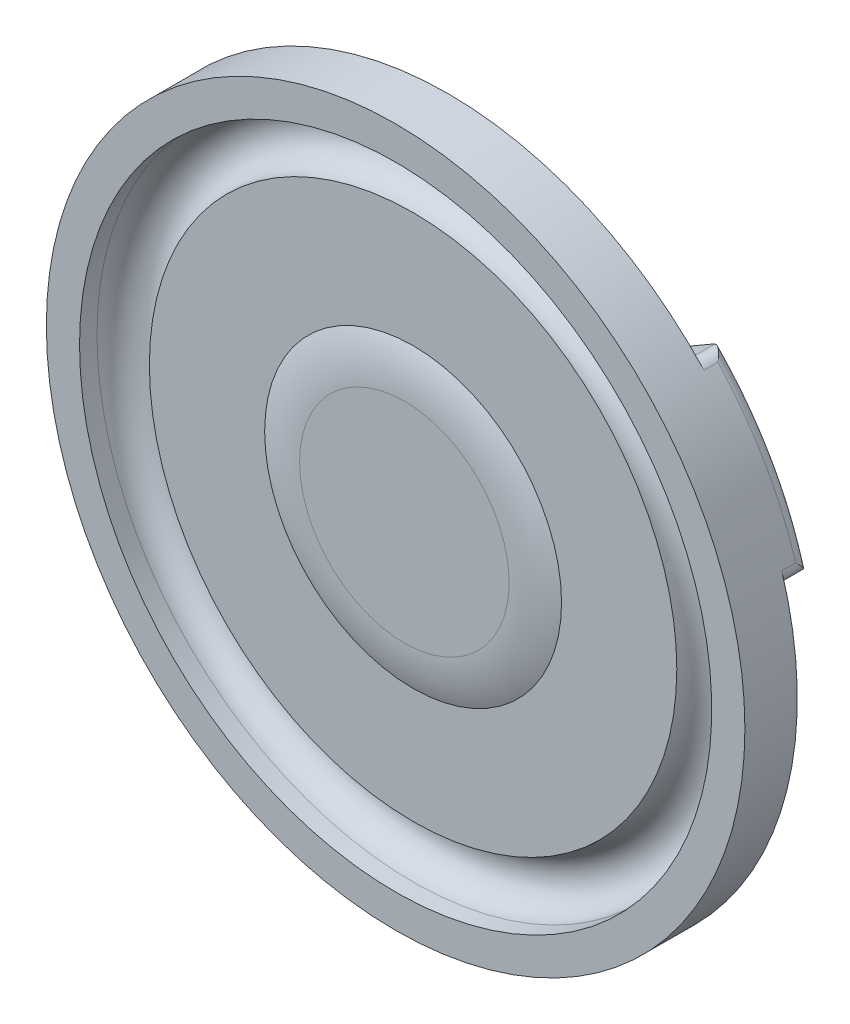
SolidWorks part; units mm, degrees
material "ABS"
ref_plane "Спереди" through (0, 0, 0) normal (0, 0, 1) x (1, 0, 0)
ref_plane "Сверху" through (0, 0, 0) normal (0, 1, 0) x (1, 0, 0)
ref_plane "Справа" through (0, 0, 0) normal (1, 0, 0) x (0, 0, -1)
ref_axis "Ось1" through (0, 0, 50) along (0, 0, -1)
sketch "Эскиз1" plane through (0, 0, 0) normal (0, 1, 0) x (1, 0, 0)
  line L0 (0, 0) -> (9.5, 0)
  line L5 (20, -3.5) -> (20, -6.5)
  line L6 (20, -6.5) -> (18.1, -6.5)
  line L11 (0, 0) -> (0, -6)
  line L12 (0, -6) -> (6, -6)
  line L13 (0, 0) -> (0, -8.5626) construction
  line L15 (18.1, -6.5) -> (18.1, -5.5)
  line L17 (15.1, -5.5) -> (8.5, -5.5)
  line L18 (20, -3.5) -> (18.3, -3.5)
  line L19 (18.3, -3.5) -> (18.3, -5.5)
  line L20 (14.9118, -5.3) -> (14.9118, -5.5) construction
  line L21 (14.9118, -5.3) -> (11.25, -5.3)
  line L23 (18.3, -5.5) -> (18.1, -5.5) construction
  line L24 (11.25, -5.3) -> (11.25, -0.01)
  line L25 (11.25, -0.01) -> (9.5, 0)
  arc A5 (18.1, -5.5) -> (15.1, -5.5) centre (16.6, -5.5) ccw
  arc A6 (6, -6) -> (8.5, -5.5) centre (6, 0.5) ccw
  arc A7 (18.3, -5.5) -> (14.9118, -5.3) centre (16.6, -5.5) ccw
  point P1 (16.6, -3.8)
  dimension "D12" = 19
  dimension "D13" = 2.5
  dimension "D2" = 22.5
  dimension "D3" = 0.01
  dimension "D4" = 3
  dimension "D5" = 1.7
  dimension "D6" = 1.9
  dimension "D7" = 6.5
  dimension "D8" = 1
  dimension "D9" = 30.2
  dimension "D10" = 0.5
  dimension "D11" = 17
  dimension "D14" = 0.3
  dimension "D18" = 40
revolve "Повернуть2" add sketch "Эскиз1" angle 360 about L11
sketch "Эскиз5" plane through (0, 0, 3.5) normal (0, 0, -1) x (-1, 0, 0)
  line L0 (0, -15.0554) -> (0, 0) construction
  line L2 (4, -19.5959) -> (4, -10.5149)
  line L3 (4, -10.5149) -> (-4, -10.5149)
  line L4 (-4, -19.5959) -> (-4, -10.5149)
  line L5 (4, -19.5959) -> (-4, -10.5149) construction
  line L6 (4, -10.5149) -> (-4, -19.5959) construction
  line L7 (0, 0) -> (8.7277, 5.0389) construction
  line L8 (11.2277, 0.7088) -> (6.2277, 9.369)
  line L9 (6.2277, 9.369) -> (14.2705, 14.0126)
  line L10 (19.2705, 5.3523) -> (11.2277, 0.7088)
  line L11 (-6.2277, 9.369) -> (-14.2705, 14.0126)
  line L12 (-19.2705, 5.3523) -> (-11.2277, 0.7088)
  line L13 (-11.2277, 0.7088) -> (-6.2277, 9.369)
  circle A0 centre (0, 0) radius 11.25 construction
  arc A2 (-4, -19.5959) -> (4, -19.5959) centre (0, 0) ccw
  arc A3 (14.2705, 14.0126) -> (19.2705, 5.3523) centre (0, 0) cw
  circle A4 centre (0, 0) radius 11.25 construction
  arc A5 (-14.2705, 14.0126) -> (-19.2705, 5.3523) centre (0, 0) ccw
  circle A6 centre (0, 0) radius 20 construction
  point P4 (0, -15.0554)
  dimension "D1" = 8
  dimension "D2" = 10
  dimension "D3" = 120
extrude "Бобышка-Вытянуть5" add sketch "Эскиз5" along normal offset from surface (1.5 mm away) 2 up to face at (-9.5, 0, 0)
fillet "Скругление1" radius 0.7 9 edges at (19.2705, 5.3523, 2.75) (4, -19.5959, 2.75) (-4, -19.5959, 2.75) (14.2705, 14.0126, 2.75) (-14.2705, 14.0126, 2.75) (-19.2705, 5.3523, 2.75) (0, -20, 2) (-17.3205, 10, 2) (17.3205, 10, 2)
sketch "Эскиз2" plane through (0, 0, 2) normal (0, 0, -1) x (-1, 0, 0)
  line L0 (3.8, -13.7859) -> (3.8, -18.9222)
  line L1 (-3.8, -13.7859) -> (-3.8, -18.9222)
  line L2 (0, 0) -> (3.8, -13.7859) construction
  line L3 (0, 0) -> (-3.8, -13.7859) construction
  line L4 (0, -14.3) -> (0, -19.3) construction
  line L6 (-4, -18.8809) -> (-4, -10.5149) construction
  arc A0 (-3.8, -13.7859) -> (3.8, -13.7859) centre (0, 0) ccw
  arc A1 (-3.8, -18.9222) -> (3.8, -18.9222) centre (0, 0) ccw
  arc A2 (-4, -18.8809) -> (4, -18.8809) centre (0, 0) ccw construction
  dimension "D1" = 5
  dimension "D2" = 0.2
extrude "Бобышка-Вытянуть2" add sketch "Эскиз2" along normal blind 0.4
sketch "Эскиз3" plane through (0, 0, 0) normal (0, 0, -1) x (-1, 0, 0)
  text T0 "4Ω 3W\r\n" font "Arial" height 3
  text T1 "−  +" font "Arial" height 4
extrude "Бобышка-Вытянуть3" add sketch "Эскиз3" along normal blind 0.01
